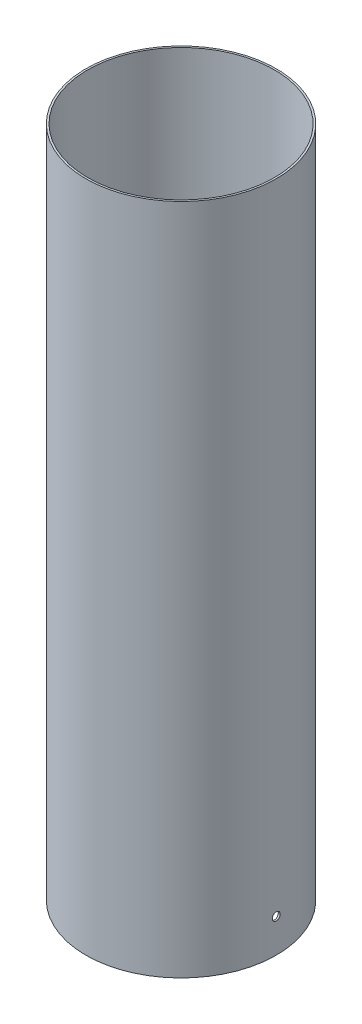
SolidWorks part; units mm, degrees
material "PBT Общее назначение"
ref_plane "Спереди" through (0, 0, 0) normal (0, 0, 1) x (1, 0, 0)
ref_plane "Сверху" through (0, 0, 0) normal (0, 1, 0) x (1, 0, 0)
ref_plane "Справа" through (0, 0, 0) normal (1, 0, 0) x (0, 0, -1)
sketch "Эскиз1" plane through (0, 0, 0) normal (0, 1, 0) x (1, 0, 0)
  circle A0 centre (0, 0) radius 51
  circle A1 centre (0, 0) radius 50
  dimension "D1" = 100
  dimension "D2" = 102
extrude "Бобышка-Вытянуть1" add sketch "Эскиз1" along normal blind 360
sketch "Эскиз2" plane through (0, 0, 0) normal (1, 0, 0) x (0, 0, -1)
  line L0 (0, 0) -> (0, 360) construction
  line L1 (50, 360) -> (-50, 360) construction
  circle A0 centre (0, 18) radius 2.1
  dimension "D1" = 4.2
  dimension "D2" = 18
extrude "Вырез-Вытянуть1" cut sketch "Эскиз2" against normal blind 129 and the other way blind 116
